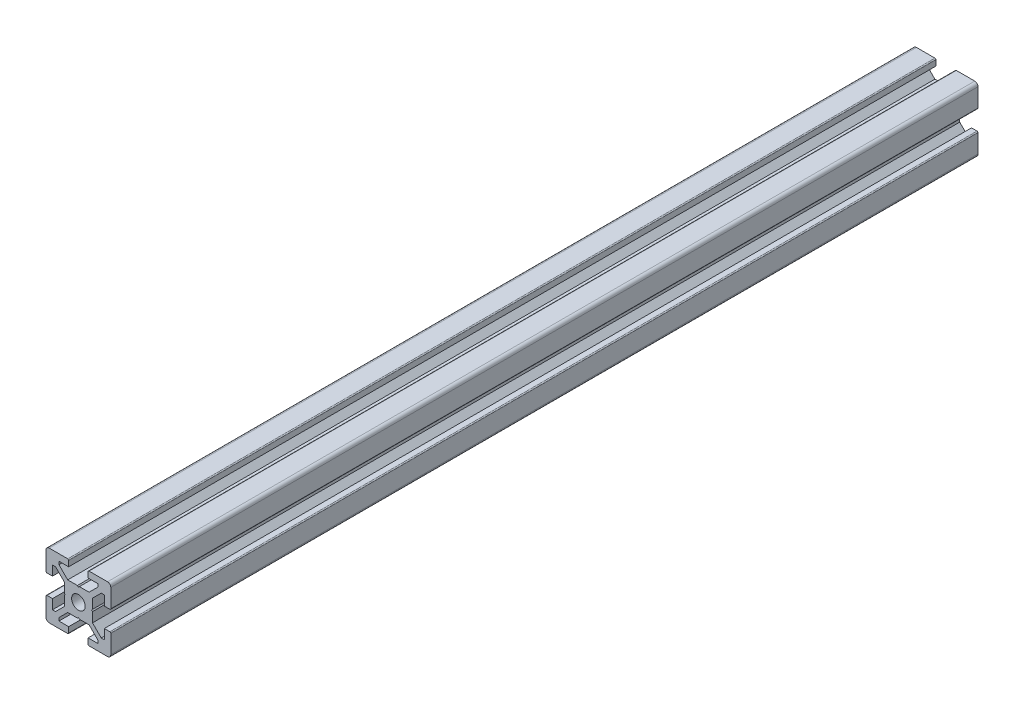
SolidWorks part; units mm, degrees
ref_plane "Front Plane" through (0, 0, 0) normal (0, 0, 1) x (1, 0, 0)
ref_plane "Top Plane" through (0, 0, 0) normal (0, 1, 0) x (1, 0, 0)
ref_plane "Right Plane" through (0, 0, 0) normal (1, 0, 0) x (0, 0, -1)
sketch "Sketch1" plane through (0, 0, 0) normal (0, 0, 1) x (1, 0, 0)
  line L0 (0, 0) -> (0, 4.3607) construction
  line L1 (-10, 10) -> (10, 10) construction
  line L2 (-10, 10) -> (-10, -10) construction
  line L3 (-10, -10) -> (10, -10) construction
  line L4 (10, 10) -> (10, -10) construction
  line L5 (-10, 10) -> (10, -10) construction
  line L6 (-10, -10) -> (10, 10) construction
  line L7 (0, 4.3607) -> (3.3, 4.3607) construction
  line L8 (3.3, 4.3607) -> (6, 7.0607)
  line L9 (6, 7.0607) -> (6, 8)
  line L10 (6, 8) -> (3, 8)
  line L11 (3, 8) -> (3, 9.7)
  line L12 (3.3, 10) -> (9, 10)
  line L13 (0, 4.0607) -> (0.3, 4.3607)
  line L14 (0.3, 4.3607) -> (3.3, 4.3607)
  line L15 (10, 3.3) -> (10, 9)
  line L16 (8, 3) -> (9.7, 3)
  line L17 (8, 6) -> (8, 3)
  line L18 (7.0607, 6) -> (8, 6)
  line L19 (4.3607, 3.3) -> (7.0607, 6)
  line L20 (4.3607, 0.3) -> (4.3607, 3.3)
  line L21 (4.0607, 0) -> (4.3607, 0.3)
  line L22 (4.0607, 0) -> (4.3607, -0.3)
  line L23 (4.3607, -0.3) -> (4.3607, -3.3)
  line L24 (4.3607, -3.3) -> (7.0607, -6)
  line L25 (7.0607, -6) -> (8, -6)
  line L26 (8, -6) -> (8, -3)
  line L27 (8, -3) -> (9.7, -3)
  line L28 (10, -3.3) -> (10, -9)
  line L29 (3.3, -10) -> (9, -10)
  line L30 (3, -8) -> (3, -9.7)
  line L31 (6, -8) -> (3, -8)
  line L32 (6, -7.0607) -> (6, -8)
  line L33 (3.3, -4.3607) -> (6, -7.0607)
  line L34 (0.3, -4.3607) -> (3.3, -4.3607)
  line L35 (0, -4.0607) -> (0.3, -4.3607)
  line L36 (0, -4.0607) -> (-0.3, -4.3607)
  line L37 (-0.3, -4.3607) -> (-3.3, -4.3607)
  line L38 (-3.3, -4.3607) -> (-6, -7.0607)
  line L39 (-6, -7.0607) -> (-6, -8)
  line L40 (-6, -8) -> (-3, -8)
  line L41 (-3, -8) -> (-3, -9.7)
  line L42 (-3.3, -10) -> (-9, -10)
  line L43 (-10, -3.3) -> (-10, -9)
  line L44 (-8, -3) -> (-9.7, -3)
  line L45 (-8, -6) -> (-8, -3)
  line L46 (-7.0607, -6) -> (-8, -6)
  line L47 (-4.3607, -3.3) -> (-7.0607, -6)
  line L48 (-4.3607, -0.3) -> (-4.3607, -3.3)
  line L49 (-4.0607, 0) -> (-4.3607, -0.3)
  line L50 (-4.0607, 0) -> (-4.3607, 0.3)
  line L51 (-4.3607, 0.3) -> (-4.3607, 3.3)
  line L52 (-4.3607, 3.3) -> (-7.0607, 6)
  line L53 (-7.0607, 6) -> (-8, 6)
  line L54 (-8, 6) -> (-8, 3)
  line L55 (-8, 3) -> (-9.7, 3)
  line L56 (-10, 3.3) -> (-10, 9)
  line L57 (-3.3, 10) -> (-9, 10)
  line L58 (-3, 8) -> (-3, 9.7)
  line L59 (-6, 8) -> (-3, 8)
  line L60 (-6, 7.0607) -> (-6, 8)
  line L61 (-3.3, 4.3607) -> (-6, 7.0607)
  line L62 (-0.3, 4.3607) -> (-3.3, 4.3607)
  line L63 (0, 4.0607) -> (-0.3, 4.3607)
  arc A0 (3, 9.7) -> (3.3, 10) centre (3.3, 9.7) cw
  arc A1 (9, 10) -> (10, 9) centre (9, 9) cw
  arc A2 (9.7, 3) -> (10, 3.3) centre (9.7, 3.3) ccw
  arc A3 (9.7, -3) -> (10, -3.3) centre (9.7, -3.3) cw
  arc A4 (10, -9) -> (9, -10) centre (9, -9) cw
  arc A5 (3, -9.7) -> (3.3, -10) centre (3.3, -9.7) ccw
  arc A6 (-3, -9.7) -> (-3.3, -10) centre (-3.3, -9.7) cw
  arc A7 (-9, -10) -> (-10, -9) centre (-9, -9) cw
  arc A8 (-9.7, -3) -> (-10, -3.3) centre (-9.7, -3.3) ccw
  arc A9 (-9.7, 3) -> (-10, 3.3) centre (-9.7, 3.3) cw
  arc A10 (-10, 9) -> (-9, 10) centre (-9, 9) cw
  arc A11 (-3, 9.7) -> (-3.3, 10) centre (-3.3, 9.7) ccw
  circle A12 centre (0, 0) radius 2.1
  point P0 (0, 0)
  point P95 (0, 0)
  dimension "D4" = 1
  dimension "D5" = 0.3
  dimension "D12" = 4.2
  dimension "D1" = 20
  dimension "D2" = 20
  dimension "D3" = 2
  dimension "D6" = 0.75
  dimension "D7" = 3
  dimension "D8" = 0.9393
  dimension "D9" = 3
  dimension "D10" = 0.3
  dimension "D11" = 4
extrude "Boss-Extrude1" add sketch "Sketch1" along normal up to surface (267.7514 mm away)
